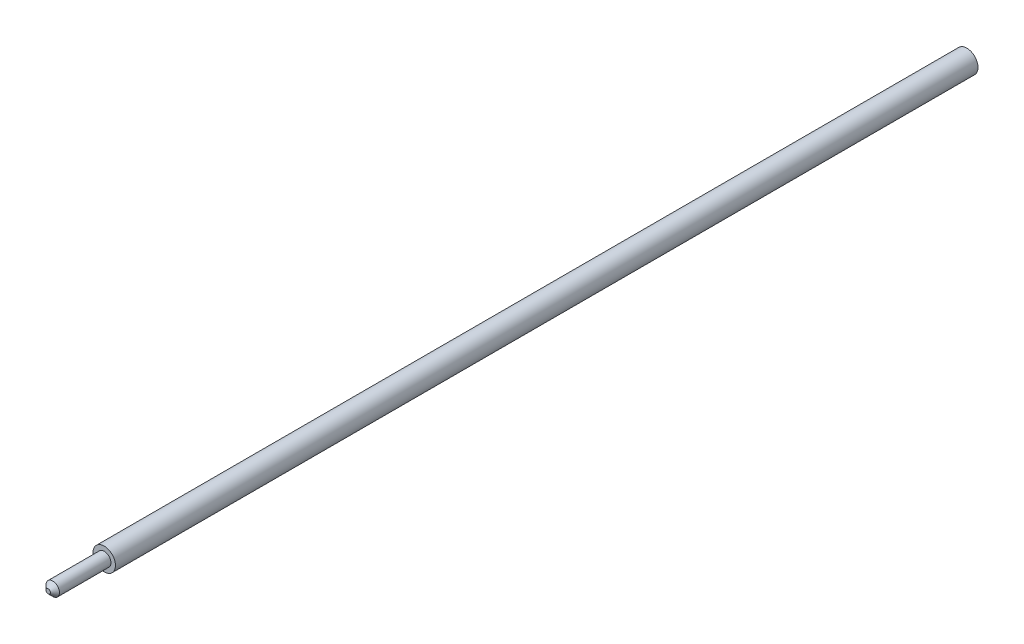
SolidWorks part; units mm, degrees
material "ABS PC"
ref_plane "Front Plane" through (0, 0, 0) normal (0, 0, 1) x (1, 0, 0)
ref_plane "Top Plane" through (0, 0, 0) normal (0, 1, 0) x (1, 0, 0)
ref_plane "Right Plane" through (0, 0, 0) normal (1, 0, 0) x (0, 0, -1)
sketch "Sketch1" plane through (0, 0, 0) normal (0, 0, 1) x (1, 0, 0)
  circle A0 centre (0, 0) radius 1.27
  dimension "D1" = 2.54
extrude "Boss-Extrude1" add sketch "Sketch1" along normal blind 97.79
sketch "Sketch3" plane through (0, 0, 97.79) normal (0, 0, 1) x (1, 0, 0)
  circle A0 centre (0, 0) radius 0.762
  dimension "D1" = 1.524
extrude "Boss-Extrude2" add sketch "Sketch3" along normal blind 6.35
ref_axis "Axis1" through (0, 0, -5.334) along (0, 0, 1)
chamfer "Chamfer1" distance 0.508 angle 45 1 edges at (0.762, 0, 104.14)
